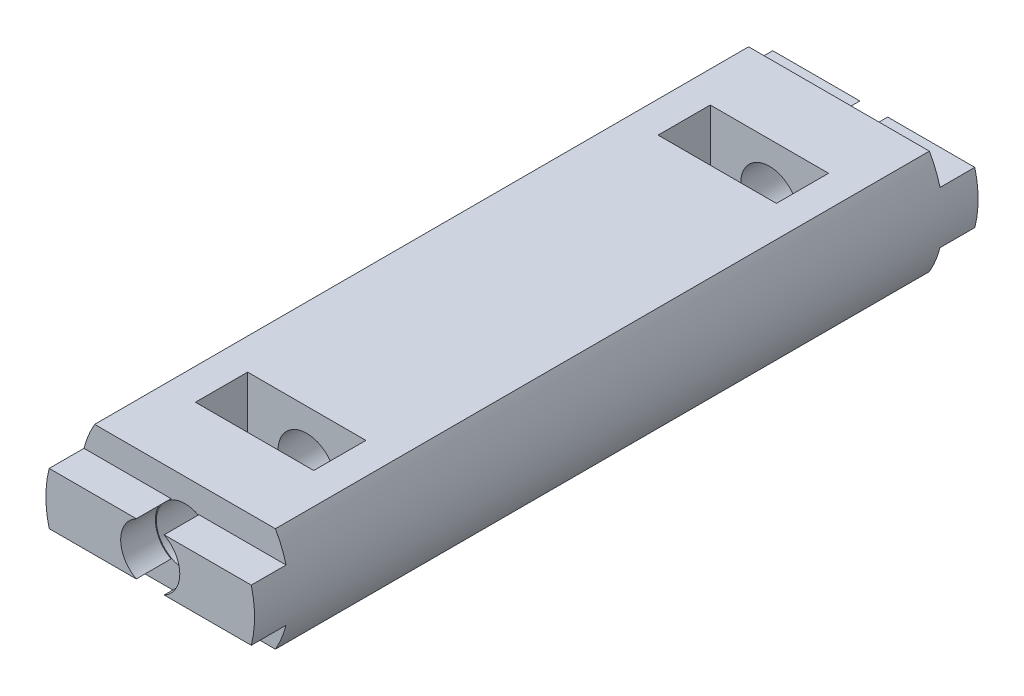
SolidWorks part; units mm, degrees
ref_plane "Plano frontal" through (0, 0, 0) normal (0, 0, 1) x (1, 0, 0)
ref_plane "Plano superior" through (0, 0, 0) normal (0, 1, 0) x (1, 0, 0)
ref_plane "Plano direito" through (0, 0, 0) normal (1, 0, 0) x (0, 0, -1)
sketch "Esboço1" plane through (0, 0, 0) normal (0, 0, 1) x (1, 0, 0)
  line L1 (-6, 0) -> (6, 0) construction
  line L2 (-5.1962, -3) -> (5.1962, -3)
  line L3 (-1.0405, 0) -> (1.3443, 0) construction
  line L4 (-5.1962, 3) -> (5.1962, 3)
  line L5 (-4.4994, 3) -> (6, 3) construction
  line L6 (-4.4994, -3) -> (6, -3) construction
  line L7 (-4.4994, 0) -> (6, 0) construction
  circle A0 centre (0, 0) radius 1.65
  arc A1 (-5.1962, 3) -> (-5.1962, -3) centre (0, 0) ccw
  arc A2 (5.1962, -3) -> (5.1962, 3) centre (0, 0) ccw
  point P5 (-7.7551, 4.567)
  point P16 (0, 9)
  point P18 (0.6344, -8.9776)
  point P19 (0, 0)
  point P20 (0, 3.66)
  dimension "D1" = 3.3
  dimension "D3" = 12
  dimension "D2" = 3
  dimension "D4" = 3
extrude "Ressalto-extrusão1" add sketch "Esboço1" along normal blind 37.6
sketch "Esboço3" plane through (0, 0, 0) normal (0, 0, -1) x (-1, 0, 0)
  line L0 (0.8, 1.5) -> (5.8095, 1.5)
  line L1 (-5.8095, 1.5) -> (-0.8, 1.5)
  line L2 (0.8, -1.5) -> (5.8095, -1.5)
  line L3 (-5.8095, -1.5) -> (-0.8, -1.5)
  arc A0 (-5.8095, 1.5) -> (-5.8095, -1.5) centre (0, 0) ccw
  arc A1 (5.8095, -1.5) -> (5.8095, 1.5) centre (0, 0) ccw
  arc A2 (-0.8, 1.5) -> (-0.8, -1.5) centre (0, 0) ccw
  circle A3 centre (0, 0) radius 6 construction
  arc A4 (0.8, -1.5) -> (0.8, 1.5) centre (0, 0) ccw
  point P1 (6, 0)
  dimension "D2" = 1.7
  dimension "D1" = 3
extrude "Ressalto-extrusão2" add sketch "Esboço3" against normal offset from surface 2 and the other way blind 2 up to face at (0, 0, 37.6) offset beyond the face yes
sketch "Esboço2" plane through (0, 0, 0) normal (0, 1, 0) x (1, 0, 0)
  line L0 (0, 0) -> (0, -37.6) construction
  line L1 (1.65, 0) -> (-1.65, 0) construction
  line L4 (-3.4, -4) -> (3.4, -4)
  line L5 (-3.4, -4) -> (-3.4, -7)
  line L6 (-3.4, -7) -> (3.4, -7)
  line L7 (3.4, -4) -> (3.4, -7)
  line L8 (-3.4, -4) -> (3.4, -7) construction
  line L9 (-3.4, -7) -> (3.4, -4) construction
  line L10 (0, 0) -> (0, -42.0111) construction
  line L11 (5.8095, 0) -> (0.8, 0) construction
  line L12 (-4.535, -18.8) -> (9.5, -18.8) construction
  line L15 (3.4, -7) -> (-3.4, -4) construction
  line L16 (3.4, -4) -> (-3.4, -7) construction
  line L17 (-3.4, -4) -> (-3.4, -7)
  line L18 (3.4, -7) -> (-3.4, -7)
  line L19 (3.4, -4) -> (3.4, -7)
  line L20 (3.4, -4) -> (-3.4, -4)
  line L21 (3.4, -33.6) -> (-3.4, -30.6) construction
  line L22 (3.4, -30.6) -> (-3.4, -33.6) construction
  line L23 (-3.4, -30.6) -> (3.4, -33.6) construction
  line L24 (-3.4, -33.6) -> (3.4, -30.6) construction
  line L25 (3.4, -33.6) -> (-3.4, -33.6)
  line L26 (3.4, -33.6) -> (3.4, -30.6)
  line L27 (3.4, -30.6) -> (-3.4, -30.6)
  line L28 (-3.4, -33.6) -> (-3.4, -30.6)
  line L29 (3.4, -33.6) -> (3.4, -30.6)
  line L30 (-3.4, -30.6) -> (3.4, -30.6)
  line L31 (-3.4, -33.6) -> (-3.4, -30.6)
  line L32 (-3.4, -33.6) -> (3.4, -33.6)
  line L33 (-5.1962, -37.6) -> (-5.1962, 0) construction
  point P6 (0, -5.5)
  point P11 (-4.535, -18.3263)
  point P16 (-5.1962, -18.8)
  point P28 (0, -5.5)
  point P37 (0, -32.1)
  point P38 (0, -32.1)
  dimension "D1" = 3
  dimension "D2" = 6.8
  dimension "D3" = 4
extrude "Corte-extrusão1" cut sketch "Esboço2" against normal through all both and the other way through all contours L7 L4 L5 L6 | L19 L20 L17 L18 | L28 L25 L26 L27 | L31 L32 L29 L30 region at (0, 0, 5.5) region at (0, 0, 32.1)
